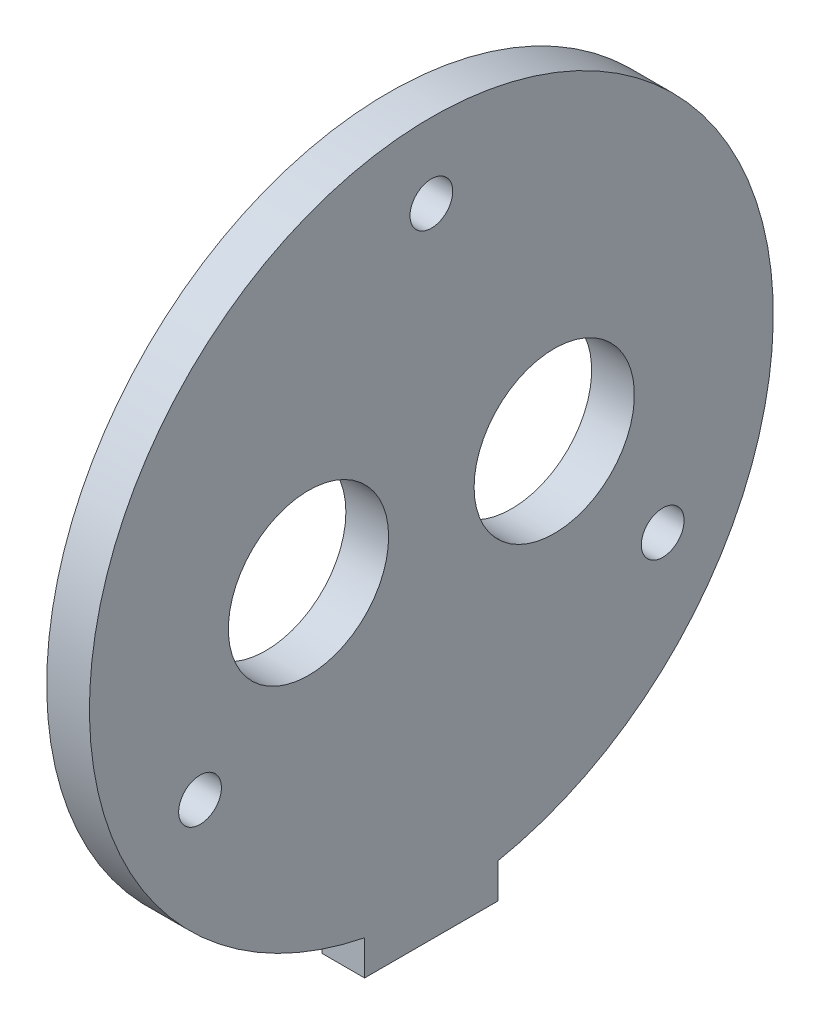
SolidWorks part; units mm, degrees
ref_plane "Front Plane" through (0, 0, 0) normal (0, 0, 1) x (1, 0, 0)
ref_plane "Top Plane" through (0, 0, 0) normal (0, 1, 0) x (1, 0, 0)
ref_plane "Right Plane" through (0, 0, 0) normal (1, 0, 0) x (0, 0, -1)
sketch "Sketch1" plane through (0, 0, 0) normal (1, 0, 0) x (0, 0, -1)
  line L0 (0, 86.3618) -> (0, -95.6447) construction
  line L1 (-89.4162, 0) -> (80.9544, 0) construction
  line L5 (-12.5, -62.7674) -> (-12.5, -69.29)
  line L6 (-12.5, -69.29) -> (12.5, -69.29)
  line L7 (12.5, -62.7674) -> (12.5, -69.29)
  circle A0 centre (0, 0) radius 76.29 construction
  circle A1 centre (0, 50) radius 4
  circle A2 centre (43.3013, -25) radius 4
  circle A3 centre (-43.3013, -25) radius 4
  circle A4 centre (-23, 0) radius 15
  circle A5 centre (23, 0) radius 15
  arc A6 (12.5, -62.7674) -> (-12.5, -62.7674) centre (0, 0) ccw
  point P14 (0, 0)
  point P16 (0, -76.29)
  point P19 (17.8909, -61.4485)
  point P20 (0, 0)
  point P21 (15, -62.2162)
  point P27 (0, -69.29)
  point P30 (0, 56.7762)
  point P31 (0, 56.7762)
  dimension "D1" = 152.58
  dimension "D2" = 8
  dimension "D5" = 30
  dimension "D9" = 7
  dimension "D7" = 64
  dimension "D3" = 50
  dimension "D6" = 23
  dimension "D8" = 25
  dimension "D4" = 3
extrude "Boss-Extrude1" add sketch "Sketch1" along normal blind 8
